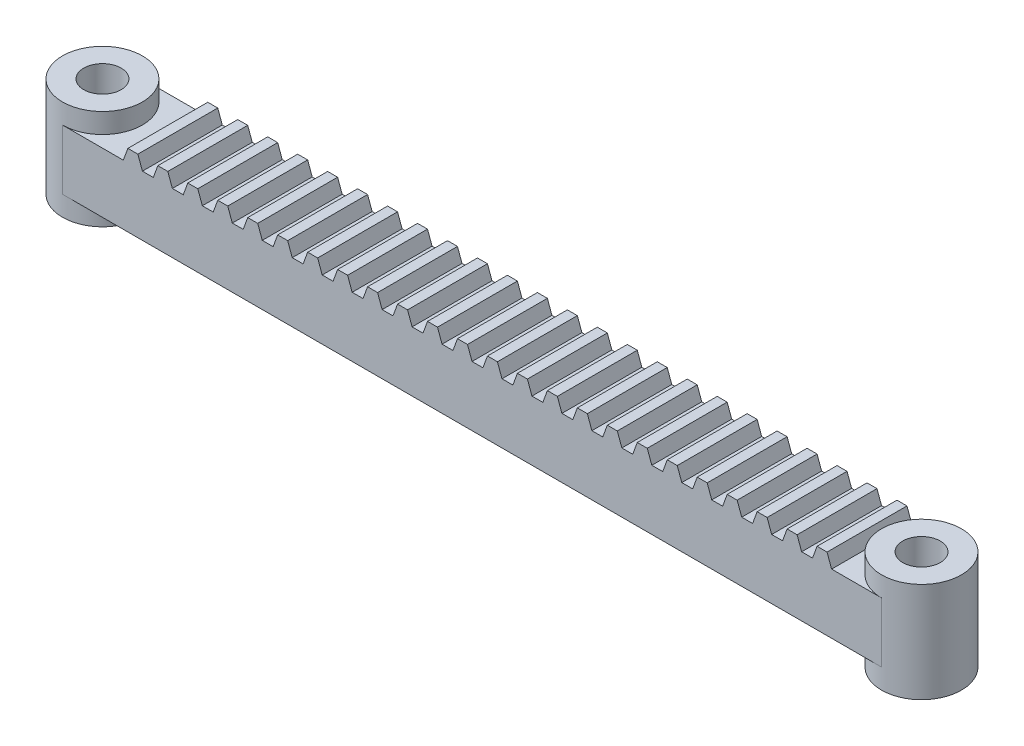
SolidWorks part; units mm, degrees
material "Galvanized Steel"
ref_plane "Front Plane" through (0, 0, 0) normal (0, 0, 1) x (1, 0, 0)
ref_plane "Top Plane" through (0, 0, 0) normal (0, 1, 0) x (1, 0, 0)
ref_plane "Right Plane" through (0, 0, 0) normal (1, 0, 0) x (0, 0, -1)
sketch "Sketch2" plane through (0, 0, 0) normal (0, 1, 0) x (1, 0, 0)
  line L1 (-82, -8) -> (82, -8)
  line L2 (-82, -8) -> (-82, 8) construction
  line L3 (-82, 8) -> (82, 8)
  line L4 (82, -8) -> (82, 8) construction
  line L5 (-82, -8) -> (82, 8) construction
  line L6 (-82, 8) -> (82, -8) construction
  circle A0 centre (-82, 0) radius 8
  circle A1 centre (82, 0) radius 8
  circle A2 centre (-82, 0) radius 3.75
  circle A3 centre (82, 0) radius 3.75
  point P0 (0, 0)
  dimension "D1" = 164
  dimension "D2" = 16
  dimension "D3" = 7.5
  dimension "D4" = 7.5
extrude "Boss-Extrude1" add sketch "Sketch2" along normal blind 20 contours A0 A2 | A1 A3 region at (-89.7737, 0, 0) region at (74.2263, 0, 0)
extrude "Boss-Extrude2" add sketch "Sketch2<3>" along normal blind 12 from offset 4 contours A1 L3 A0 L1 region at (0, 0, 0)
sketch "Sketch2<3>" plane through (0, 0, 0) normal (0, 1, 0) x (1, 0, 0) same geometry as "Sketch2"
sketch "Sketch3" plane through (0, 0, 8) normal (0, 0, 1) x (1, 0, 0)
  line L0 (72, 16) -> (71.0901, 18.5)
  line L1 (-82, 16) -> (82, 16) construction
  line L2 (71.0901, 18.5) -> (69.0901, 18.5)
  line L3 (69.0901, 18.5) -> (68.1801, 16)
  line L4 (68.1801, 16) -> (66, 16)
  line L5 (66, 16) -> (65.0901, 18.5)
  line L6 (65.0901, 18.5) -> (63.0901, 18.5)
  line L7 (63.0901, 18.5) -> (62.1801, 16)
  line L8 (82, 16) -> (74, 16) construction
  line L9 (57.0901, 18.5) -> (56.1801, 16)
  line L10 (72, 16) -> (42, 16) construction
  line L11 (59.0901, 18.5) -> (57.0901, 18.5)
  line L12 (62.1801, 16) -> (60, 16)
  line L13 (60, 16) -> (59.0901, 18.5)
  line L14 (63.0901, 18.5) -> (62.1801, 16)
  line L15 (65.0901, 18.5) -> (63.0901, 18.5)
  line L16 (66, 16) -> (65.0901, 18.5)
  line L17 (51.0901, 18.5) -> (50.1801, 16)
  line L18 (53.0901, 18.5) -> (51.0901, 18.5)
  line L19 (56.1801, 16) -> (54, 16)
  line L20 (54, 16) -> (53.0901, 18.5)
  line L21 (57.0901, 18.5) -> (56.1801, 16)
  line L22 (59.0901, 18.5) -> (57.0901, 18.5)
  line L23 (60, 16) -> (59.0901, 18.5)
  line L24 (45.0901, 18.5) -> (44.1801, 16)
  line L25 (47.0901, 18.5) -> (45.0901, 18.5)
  line L26 (50.1801, 16) -> (48, 16)
  line L27 (48, 16) -> (47.0901, 18.5)
  line L28 (51.0901, 18.5) -> (50.1801, 16)
  line L29 (53.0901, 18.5) -> (51.0901, 18.5)
  line L30 (54, 16) -> (53.0901, 18.5)
  line L31 (39.0901, 18.5) -> (38.1801, 16)
  line L32 (41.0901, 18.5) -> (39.0901, 18.5)
  line L33 (44.1801, 16) -> (42, 16)
  line L34 (42, 16) -> (41.0901, 18.5)
  line L35 (45.0901, 18.5) -> (44.1801, 16)
  line L36 (47.0901, 18.5) -> (45.0901, 18.5)
  line L37 (48, 16) -> (47.0901, 18.5)
  line L38 (33.0901, 18.5) -> (32.1801, 16)
  line L39 (35.0901, 18.5) -> (33.0901, 18.5)
  line L40 (38.1801, 16) -> (36, 16)
  line L41 (36, 16) -> (35.0901, 18.5)
  line L42 (39.0901, 18.5) -> (38.1801, 16)
  line L43 (41.0901, 18.5) -> (39.0901, 18.5)
  line L44 (42, 16) -> (41.0901, 18.5)
  line L45 (27.0901, 18.5) -> (26.1801, 16)
  line L46 (29.0901, 18.5) -> (27.0901, 18.5)
  line L47 (32.1801, 16) -> (30, 16)
  line L48 (30, 16) -> (29.0901, 18.5)
  line L49 (33.0901, 18.5) -> (32.1801, 16)
  line L50 (35.0901, 18.5) -> (33.0901, 18.5)
  line L51 (36, 16) -> (35.0901, 18.5)
  line L52 (21.0901, 18.5) -> (20.1801, 16)
  line L53 (23.0901, 18.5) -> (21.0901, 18.5)
  line L54 (26.1801, 16) -> (24, 16)
  line L55 (24, 16) -> (23.0901, 18.5)
  line L56 (27.0901, 18.5) -> (26.1801, 16)
  line L57 (29.0901, 18.5) -> (27.0901, 18.5)
  line L58 (30, 16) -> (29.0901, 18.5)
  line L59 (15.0901, 18.5) -> (14.1801, 16)
  line L60 (17.0901, 18.5) -> (15.0901, 18.5)
  line L61 (20.1801, 16) -> (18, 16)
  line L62 (18, 16) -> (17.0901, 18.5)
  line L63 (21.0901, 18.5) -> (20.1801, 16)
  line L64 (23.0901, 18.5) -> (21.0901, 18.5)
  line L65 (24, 16) -> (23.0901, 18.5)
  line L66 (9.0901, 18.5) -> (8.1801, 16)
  line L67 (11.0901, 18.5) -> (9.0901, 18.5)
  line L68 (14.1801, 16) -> (12, 16)
  line L69 (12, 16) -> (11.0901, 18.5)
  line L70 (15.0901, 18.5) -> (14.1801, 16)
  line L71 (17.0901, 18.5) -> (15.0901, 18.5)
  line L72 (18, 16) -> (17.0901, 18.5)
  line L73 (3.0901, 18.5) -> (2.1801, 16)
  line L74 (5.0901, 18.5) -> (3.0901, 18.5)
  line L75 (8.1801, 16) -> (6, 16)
  line L76 (6, 16) -> (5.0901, 18.5)
  line L77 (9.0901, 18.5) -> (8.1801, 16)
  line L78 (11.0901, 18.5) -> (9.0901, 18.5)
  line L79 (12, 16) -> (11.0901, 18.5)
  line L80 (-2.9099, 18.5) -> (-3.8199, 16)
  line L81 (-0.9099, 18.5) -> (-2.9099, 18.5)
  line L82 (2.1801, 16) -> (0, 16)
  line L83 (0, 16) -> (-0.9099, 18.5)
  line L84 (3.0901, 18.5) -> (2.1801, 16)
  line L85 (5.0901, 18.5) -> (3.0901, 18.5)
  line L86 (6, 16) -> (5.0901, 18.5)
  line L87 (-8.9099, 18.5) -> (-9.8199, 16)
  line L88 (-6.9099, 18.5) -> (-8.9099, 18.5)
  line L89 (-3.8199, 16) -> (-6, 16)
  line L90 (-6, 16) -> (-6.9099, 18.5)
  line L91 (-2.9099, 18.5) -> (-3.8199, 16)
  line L92 (-0.9099, 18.5) -> (-2.9099, 18.5)
  line L93 (0, 16) -> (-0.9099, 18.5)
  line L94 (-14.9099, 18.5) -> (-15.8199, 16)
  line L95 (-12.9099, 18.5) -> (-14.9099, 18.5)
  line L96 (-9.8199, 16) -> (-12, 16)
  line L97 (-12, 16) -> (-12.9099, 18.5)
  line L98 (-8.9099, 18.5) -> (-9.8199, 16)
  line L99 (-6.9099, 18.5) -> (-8.9099, 18.5)
  line L100 (-6, 16) -> (-6.9099, 18.5)
  line L101 (-20.9099, 18.5) -> (-21.8199, 16)
  line L102 (-18.9099, 18.5) -> (-20.9099, 18.5)
  line L103 (-15.8199, 16) -> (-18, 16)
  line L104 (-18, 16) -> (-18.9099, 18.5)
  line L105 (-14.9099, 18.5) -> (-15.8199, 16)
  line L106 (-12.9099, 18.5) -> (-14.9099, 18.5)
  line L107 (-12, 16) -> (-12.9099, 18.5)
  line L108 (-26.9099, 18.5) -> (-27.8199, 16)
  line L109 (-24.9099, 18.5) -> (-26.9099, 18.5)
  line L110 (-21.8199, 16) -> (-24, 16)
  line L111 (-24, 16) -> (-24.9099, 18.5)
  line L112 (-20.9099, 18.5) -> (-21.8199, 16)
  line L113 (-18.9099, 18.5) -> (-20.9099, 18.5)
  line L114 (-18, 16) -> (-18.9099, 18.5)
  line L115 (-32.9099, 18.5) -> (-33.8199, 16)
  line L116 (-30.9099, 18.5) -> (-32.9099, 18.5)
  line L117 (-27.8199, 16) -> (-30, 16)
  line L118 (-30, 16) -> (-30.9099, 18.5)
  line L119 (-26.9099, 18.5) -> (-27.8199, 16)
  line L120 (-24.9099, 18.5) -> (-26.9099, 18.5)
  line L121 (-24, 16) -> (-24.9099, 18.5)
  line L122 (-38.9099, 18.5) -> (-39.8199, 16)
  line L123 (-36.9099, 18.5) -> (-38.9099, 18.5)
  line L124 (-33.8199, 16) -> (-36, 16)
  line L125 (-36, 16) -> (-36.9099, 18.5)
  line L126 (-32.9099, 18.5) -> (-33.8199, 16)
  line L127 (-30.9099, 18.5) -> (-32.9099, 18.5)
  line L128 (-30, 16) -> (-30.9099, 18.5)
  line L129 (-44.9099, 18.5) -> (-45.8199, 16)
  line L130 (-42.9099, 18.5) -> (-44.9099, 18.5)
  line L131 (-39.8199, 16) -> (-42, 16)
  line L132 (-42, 16) -> (-42.9099, 18.5)
  line L133 (-38.9099, 18.5) -> (-39.8199, 16)
  line L134 (-36.9099, 18.5) -> (-38.9099, 18.5)
  line L135 (-36, 16) -> (-36.9099, 18.5)
  line L136 (-50.9099, 18.5) -> (-51.8199, 16)
  line L137 (-48.9099, 18.5) -> (-50.9099, 18.5)
  line L138 (-45.8199, 16) -> (-48, 16)
  line L139 (-48, 16) -> (-48.9099, 18.5)
  line L140 (-44.9099, 18.5) -> (-45.8199, 16)
  line L141 (-42.9099, 18.5) -> (-44.9099, 18.5)
  line L142 (-42, 16) -> (-42.9099, 18.5)
  line L143 (-56.9099, 18.5) -> (-57.8199, 16)
  line L144 (-54.9099, 18.5) -> (-56.9099, 18.5)
  line L145 (-51.8199, 16) -> (-54, 16)
  line L146 (-54, 16) -> (-54.9099, 18.5)
  line L147 (-50.9099, 18.5) -> (-51.8199, 16)
  line L148 (-48.9099, 18.5) -> (-50.9099, 18.5)
  line L149 (-48, 16) -> (-48.9099, 18.5)
  line L150 (-62.9099, 18.5) -> (-63.8199, 16)
  line L151 (-60.9099, 18.5) -> (-62.9099, 18.5)
  line L152 (-57.8199, 16) -> (-60, 16)
  line L153 (-60, 16) -> (-60.9099, 18.5)
  line L154 (-56.9099, 18.5) -> (-57.8199, 16)
  line L155 (-54.9099, 18.5) -> (-56.9099, 18.5)
  line L156 (-54, 16) -> (-54.9099, 18.5)
  line L157 (-68.9099, 18.5) -> (-69.8199, 16)
  line L158 (-66.9099, 18.5) -> (-68.9099, 18.5)
  line L159 (-63.8199, 16) -> (-66, 16)
  line L160 (-66, 16) -> (-66.9099, 18.5)
  line L161 (-62.9099, 18.5) -> (-63.8199, 16)
  line L162 (-60.9099, 18.5) -> (-62.9099, 18.5)
  line L163 (-60, 16) -> (-60.9099, 18.5)
  line L164 (72, 16) -> (-69.8199, 16)
  line M12 (82, 16) -> (-82, 16)
  dimension "D1" = 2
  dimension "D2" = 40
  dimension "D3" = 40
  dimension "D4" = 2
  dimension "D5" = 2.5
  dimension "D6" = 2.5
  dimension "D7" = 6
  dimension "D8" = 18
  dimension "D9" = 23
  dimension "D10" = 6
extrude "Boss-Extrude3" add sketch "Sketch3" against normal up to surface (16 mm away) contours L160 L158 L157 M12 | L153 L151 L150 M12 | L146 L144 L143 M12 | L139 L137 L136 M12 | L132 L130 L129 M12 | L125 L123 L122 M12 | L118 L116 L115 M12 | L111 L109 L108 M12 | L104 L102 L101 M12 | L97 L95 L94 M12 | L90 L88 L87 M12 | L83 L81 L80 M12 | L76 L74 L73 M12 | L69 L67 L66 M12 | L62 L60 L59 M12 | L55 L53 L52 M12 | L48 L46 L45 M12 | L41 L39 L38 M12 | L34 L32 L31 M12 | L27 L25 L24 M12 | L20 L18 L17 M12 | L13 L11 L9 M12 | L6 L7 L5 M12 | L2 L3 L0 M12 region at (70.0901, 17.1197, 8) region at (-67.9099, 17.1197, 8) region at (-61.9099, 17.1197, 8) region at (-55.9099, 17.1197, 8) region at (-49.9099, 17.1197, 8) region at (-43.9099, 17.1197, 8) region at (-37.9099, 17.1197, 8) region at (-31.9099, 17.1197, 8) region at (-25.9099, 17.1197, 8) region at (-19.9099, 17.1197, 8) region at (-13.9099, 17.1197, 8) region at (-7.9099, 17.1197, 8) region at (-1.9099, 17.1197, 8) region at (4.0901, 17.1197, 8) region at (10.0901, 17.1197, 8) region at (16.0901, 17.1197, 8) region at (22.0901, 17.1197, 8) region at (28.0901, 17.1197, 8) region at (34.0901, 17.1197, 8) region at (40.0901, 17.1197, 8) region at (46.0901, 17.1197, 8) region at (52.0901, 17.1197, 8) region at (58.0901, 17.1197, 8) region at (64.0901, 17.1197, 8) up to face at (0, 10, -8)
